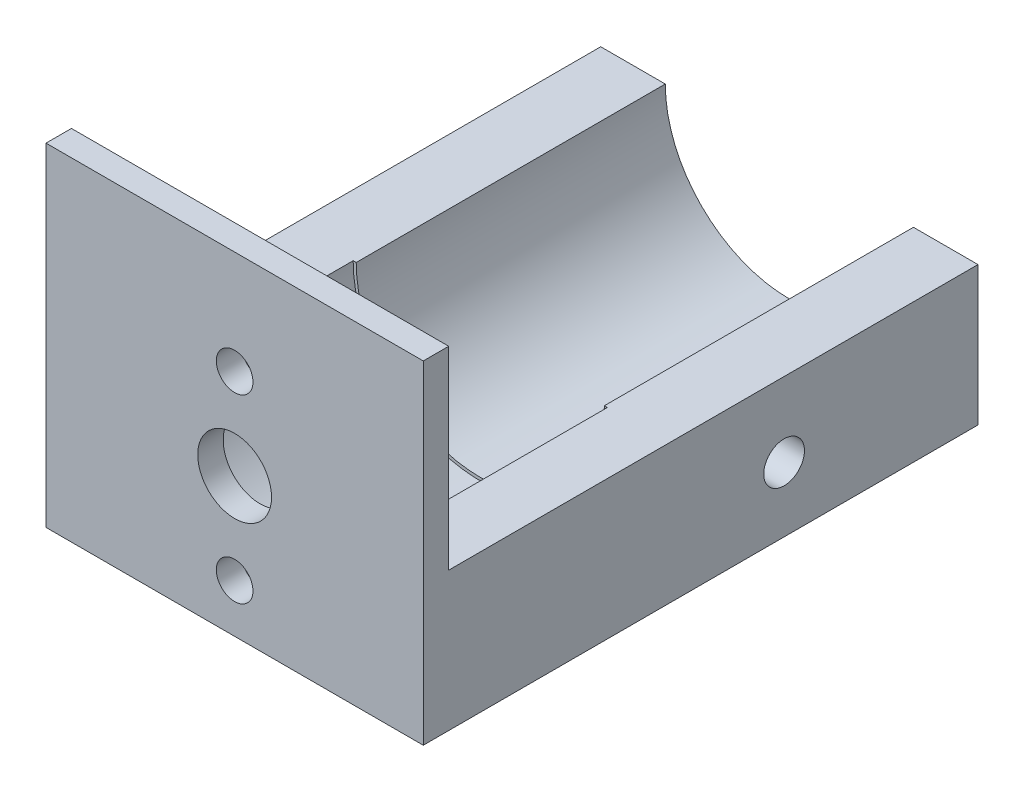
SolidWorks part; units mm, degrees
ref_plane "Front Plane" through (0, 0, 0) normal (0, 0, 1) x (1, 0, 0)
ref_plane "Top Plane" through (0, 0, 0) normal (0, 1, 0) x (1, 0, 0)
ref_plane "Right Plane" through (0, 0, 0) normal (1, 0, 0) x (0, 0, -1)
sketch "Sketch1" plane through (0, 0, 0) normal (0, 0, 1) x (1, 0, 0)
  line L7 (23.7638, 19.05) -> (23.7638, 5.4)
  line L10 (-13.3009, 19.05) -> (-13.3009, 5.4)
  line L12 (-13.3009, 19.05) -> (-6.9589, 19.05)
  line L13 (23.7638, 19.05) -> (17.4218, 19.05)
  line L14 (-13.3009, 5.4) -> (23.7638, 5.4)
  arc A1 (17.4218, 19.05) -> (-6.9589, 19.05) centre (5.2314, 19.05) cw
  dimension "D2" = 6.342
  dimension "D1" = 13.65
  dimension "D3" = 6.342
  dimension "D5" = 37.0648
extrude "Boss-Extrude1" add sketch "Sketch1" along normal blind 30.365
sketch "Sketch3" plane through (0, 0, 30.365) normal (0, 0, 1) x (1, 0, 0)
  line L1 (-13.3009, 19.05) -> (-13.3009, 5.4)
  line L3 (-13.3009, 5.4) -> (23.7638, 5.4)
  line L14 (-13.3009, 19.05) -> (-7.2589, 19.05)
  line L15 (-6.9589, 19.05) -> (-13.3009, 19.05) construction
  line L16 (17.7218, 19.05) -> (23.7638, 19.05)
  line L17 (23.7638, 19.05) -> (23.7638, 5.4)
  arc A0 (17.7218, 19.05) -> (-7.2589, 19.05) centre (5.2314, 19.05) cw
  dimension "D1" = 6.042
  dimension "D2" = 13.65
  dimension "D4" = 37.0648
extrude "Boss-Extrude2" add sketch "Sketch3" along normal blind 21.635
sketch "Sketch4" plane through (0, 0, 52) normal (0, 0, 1) x (1, 0, 0)
  line L1 (-13.3009, 5.4) -> (23.7638, 5.4)
  line L2 (-13.3009, 5.4) -> (-13.3009, 38.1)
  line L3 (-13.3009, 38.1) -> (23.7638, 38.1)
  line L4 (23.7638, 5.4) -> (23.7638, 38.1)
  circle A0 centre (5.2314, 19.05) radius 3.625
  circle A1 centre (5.2314, 10.16) radius 1.8
  circle A2 centre (5.2314, 27.94) radius 1.8
  dimension "D4" = 18.5324
  dimension "D5" = 7.25
  dimension "D6" = 3.6
  dimension "D7" = 3.6
  dimension "D10" = 8.89
  dimension "D11" = 8.89
  dimension "D1" = 37.0648
  dimension "D2" = 32.7
  dimension "D3" = 13.65
  dimension "D8" = 0
  dimension "D9" = 0
extrude "Boss-Extrude3" add sketch "Sketch4" along normal blind 2.5
sketch "Sketch5" plane through (0, 5.4, 0) normal (0, -1, 0) x (1, 0, 0)
  line L0 (-13.3009, 54.5) -> (-13.3009, 0) construction
  line L1 (-13.3009, 54.5) -> (23.7638, 54.5) construction
  line L2 (23.7638, 54.5) -> (23.7638, 0) construction
  line L3 (-13.3009, 0) -> (23.7638, 0) construction
  circle A0 centre (-8.2209, 48.15) radius 2
  circle A1 centre (18.6838, 48.15) radius 2
  circle A2 centre (-8.2209, 6.35) radius 2
  circle A3 centre (18.6838, 6.35) radius 2
  dimension "D1" = 4
  dimension "D2" = 4
  dimension "D3" = 4
  dimension "D4" = 4
  dimension "D6" = 6.35
  dimension "D7" = 5.08
  dimension "D8" = 6.35
  dimension "D9" = 5.08
  dimension "D10" = 6.35
  dimension "D11" = 5.08
  dimension "D12" = 6.35
  dimension "D5" = 5.08
extrude "Cut-Extrude1" cut sketch "Sketch5" against normal blind 7
sketch "Sketch6" plane through (-13.3009, 0, 0) normal (-1, 0, 0) x (0, 0, 1)
  line L0 (0, 19.05) -> (0, 5.4) construction
  line L1 (54.5, 5.4) -> (0, 5.4) construction
  circle A0 centre (19.05, 11.75) radius 2
  dimension "D1" = 4
  dimension "D2" = 19.05
  dimension "D3" = 6.35
extrude "Cut-Extrude2" cut sketch "Sketch6" against normal blind 7
sketch "Sketch7" plane through (23.7638, 0, 0) normal (1, 0, 0) x (0, 0, -1)
  line L0 (0, 5.4) -> (0, 19.05) construction
  line L1 (-54.5, 5.4) -> (0, 5.4) construction
  circle A0 centre (-19.05, 11.75) radius 2
  dimension "D1" = 4
  dimension "D2" = 19.05
  dimension "D3" = 6.35
extrude "Cut-Extrude3" cut sketch "Sketch7" against normal blind 7
